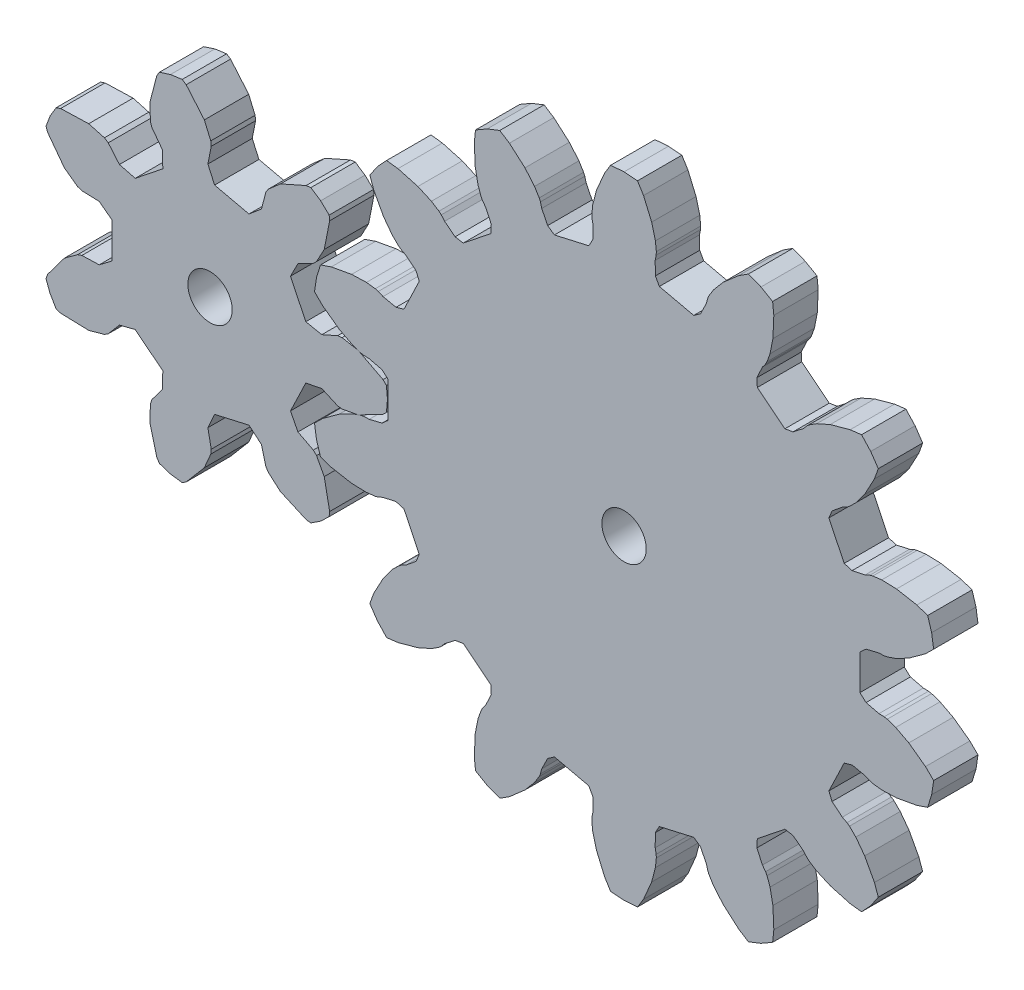
SolidWorks part; units mm, degrees
material "Corrugated Paper"
ref_plane "Front Plane" through (0, 0, 0) normal (0, 0, 1) x (1, 0, 0)
ref_plane "Top Plane" through (0, 0, 0) normal (0, 1, 0) x (1, 0, 0)
ref_plane "Right Plane" through (0, 0, 0) normal (1, 0, 0) x (0, 0, -1)
sketch "Model" plane through (0, 0, 0) normal (0, 0, 1) x (1, 0, 0)
  line L0 (10.824, -15.5893) -> (11.8775, -14.8939)
  line L1 (11.8775, -14.8939) -> (12.7899, -14.0216)
  line L2 (12.7899, -14.0216) -> (12.8434, -13.5144)
  line L3 (12.8434, -13.5144) -> (12.2623, -10.5576)
  line L4 (12.2623, -10.5576) -> (11.4342, -9.0171)
  line L5 (11.4342, -9.0171) -> (11.0892, -8.677)
  line L6 (11.0892, -8.677) -> (9.4401, -7.8202)
  line L7 (9.4401, -7.8202) -> (8.6391, -6.2612)
  line L8 (8.6391, -6.2612) -> (10.2816, -2.8505)
  line L9 (10.2816, -2.8505) -> (11.9999, -2.5047)
  line L10 (11.9999, -2.5047) -> (13.698, -3.2599)
  line L11 (13.698, -3.2599) -> (14.179, -3.3175)
  line L12 (14.179, -3.3175) -> (15.8632, -3.0111)
  line L13 (15.8632, -3.0111) -> (15.2951, -3.2054)
  line L14 (15.2951, -3.2054) -> (13.8858, -3.9376)
  line L15 (13.8858, -3.9376) -> (12.0928, -5.2415)
  line L16 (12.0928, -5.2415) -> (11.2168, -6.1052)
  line L17 (11.2168, -6.1052) -> (11.4324, -7.536)
  line L18 (11.4324, -7.536) -> (11.8589, -8.9187)
  line L19 (11.8589, -8.9187) -> (13.023, -9.3169)
  line L20 (13.023, -9.3169) -> (15.2041, -9.7136)
  line L21 (15.2041, -9.7136) -> (16.7916, -9.7618)
  line L22 (16.7916, -9.7618) -> (17.7443, -9.6477)
  line L23 (17.7443, -9.6477) -> (18.0633, -9.5598)
  line L24 (18.0633, -9.5598) -> (18.5734, -9.3329)
  line L25 (18.5734, -9.3329) -> (19.9687, -9.0348)
  line L26 (19.9687, -9.0348) -> (20.819, -9.2793)
  line L27 (20.819, -9.2793) -> (22.4615, -12.6899)
  line L28 (22.4615, -12.6899) -> (22.1225, -13.5071)
  line L29 (22.1225, -13.5071) -> (21.0194, -14.4122)
  line L30 (21.0194, -14.4122) -> (20.524, -14.6696)
  line L31 (20.524, -14.6696) -> (20.2564, -14.8641)
  line L32 (20.2564, -14.8641) -> (19.5731, -15.5378)
  line L33 (19.5731, -15.5378) -> (18.621, -16.809)
  line L34 (18.621, -16.809) -> (17.5714, -18.7617)
  line L35 (17.5714, -18.7617) -> (17.1569, -19.92)
  line L36 (17.1569, -19.92) -> (17.972, -21.1155)
  line L37 (17.972, -21.1155) -> (18.9562, -22.1762)
  line L38 (18.9562, -22.1762) -> (20.1777, -22.0299)
  line L39 (20.1777, -22.0299) -> (22.3149, -21.441)
  line L40 (22.3149, -21.441) -> (23.7661, -20.7956)
  line L41 (23.7661, -20.7956) -> (24.575, -20.2794)
  line L42 (24.575, -20.2794) -> (24.8242, -20.0619)
  line L43 (24.8242, -20.0619) -> (25.1854, -19.6361)
  line L44 (25.1854, -19.6361) -> (26.3132, -18.7621)
  line L45 (26.3132, -18.7621) -> (27.1854, -18.6134)
  line L46 (27.1854, -18.6134) -> (30.145, -20.9737)
  line L47 (30.145, -20.9737) -> (30.1941, -21.8571)
  line L48 (30.1941, -21.8571) -> (29.593, -23.151)
  line L49 (29.593, -23.151) -> (29.2583, -23.5979)
  line L50 (29.2583, -23.5979) -> (29.1016, -23.8893)
  line L51 (29.1016, -23.8893) -> (28.7783, -24.7928)
  line L52 (28.7783, -24.7928) -> (28.4721, -26.3512)
  line L53 (28.4721, -26.3512) -> (28.3736, -28.5659)
  line L54 (28.3736, -28.5659) -> (28.5027, -29.7893)
  line L55 (28.5027, -29.7893) -> (29.7558, -30.5128)
  line L56 (29.7558, -30.5128) -> (31.1028, -31.0414)
  line L57 (31.1028, -31.0414) -> (32.1398, -30.3796)
  line L58 (32.1398, -30.3796) -> (33.8099, -28.9217)
  line L59 (33.8099, -28.9217) -> (34.8374, -27.7106)
  line L60 (34.8374, -27.7106) -> (35.3421, -26.8946)
  line L61 (35.3421, -26.8946) -> (35.4723, -26.5904)
  line L62 (35.4723, -26.5904) -> (35.613, -26.0501)
  line L63 (35.613, -26.0501) -> (36.2499, -24.7734)
  line L64 (36.2499, -24.7734) -> (36.9712, -24.261)
  line L65 (36.9712, -24.261) -> (40.6618, -25.1033)
  line L66 (40.6618, -25.1033) -> (41.0893, -25.8779)
  line L67 (41.0893, -25.8779) -> (41.1092, -27.3046)
  line L68 (41.1092, -27.3046) -> (41.0015, -27.8524)
  line L69 (41.0015, -27.8524) -> (40.9868, -28.183)
  line L70 (40.9868, -28.183) -> (41.0875, -29.1372)
  line L71 (41.0875, -29.1372) -> (41.4877, -30.6741)
  line L72 (41.4877, -30.6741) -> (42.3599, -32.7123)
  line L73 (42.3599, -32.7123) -> (43.0071, -33.7585)
  line L74 (43.0071, -33.7585) -> (44.45, -33.8667)
  line L75 (44.45, -33.8667) -> (45.8929, -33.7585)
  line L76 (45.8929, -33.7585) -> (46.5401, -32.7123)
  line L77 (46.5401, -32.7123) -> (47.4123, -30.6741)
  line L78 (47.4123, -30.6741) -> (47.8125, -29.1372)
  line L79 (47.8125, -29.1372) -> (47.9132, -28.183)
  line L80 (47.9132, -28.183) -> (47.8985, -27.8524)
  line L81 (47.8985, -27.8524) -> (47.7908, -27.3046)
  line L82 (47.7908, -27.3046) -> (47.8107, -25.8779)
  line L83 (47.8107, -25.8779) -> (48.2382, -25.1033)
  line L84 (48.2382, -25.1033) -> (51.9288, -24.261)
  line L85 (51.9288, -24.261) -> (52.6501, -24.7734)
  line L86 (52.6501, -24.7734) -> (53.287, -26.0501)
  line L87 (53.287, -26.0501) -> (53.4277, -26.5904)
  line L88 (53.4277, -26.5904) -> (53.5579, -26.8946)
  line L89 (53.5579, -26.8946) -> (54.0626, -27.7106)
  line L90 (54.0626, -27.7106) -> (55.0901, -28.9217)
  line L91 (55.0901, -28.9217) -> (56.7602, -30.3796)
  line L92 (56.7602, -30.3796) -> (57.7972, -31.0414)
  line L93 (57.7972, -31.0414) -> (59.1442, -30.5128)
  line L94 (59.1442, -30.5128) -> (60.3973, -29.7893)
  line L95 (60.3973, -29.7893) -> (60.5264, -28.5659)
  line L96 (60.5264, -28.5659) -> (60.4279, -26.3512)
  line L97 (60.4279, -26.3512) -> (60.1217, -24.7928)
  line L98 (60.1217, -24.7928) -> (59.7984, -23.8893)
  line L99 (59.7984, -23.8893) -> (59.6417, -23.5979)
  line L100 (59.6417, -23.5979) -> (59.307, -23.151)
  line L101 (59.307, -23.151) -> (58.7059, -21.8571)
  line L102 (58.7059, -21.8571) -> (58.755, -20.9737)
  line L103 (58.755, -20.9737) -> (61.7146, -18.6134)
  line L104 (61.7146, -18.6134) -> (62.5868, -18.7621)
  line L105 (62.5868, -18.7621) -> (63.7146, -19.6361)
  line L106 (63.7146, -19.6361) -> (64.0758, -20.0619)
  line L107 (64.0758, -20.0619) -> (64.325, -20.2794)
  line L108 (64.325, -20.2794) -> (65.1339, -20.7956)
  line L109 (65.1339, -20.7956) -> (66.5851, -21.441)
  line L110 (66.5851, -21.441) -> (68.7223, -22.0299)
  line L111 (68.7223, -22.0299) -> (69.9438, -22.1762)
  line L112 (69.9438, -22.1762) -> (70.928, -21.1155)
  line L113 (70.928, -21.1155) -> (71.7431, -19.92)
  line L114 (71.7431, -19.92) -> (71.3286, -18.7617)
  line L115 (71.3286, -18.7617) -> (70.279, -16.809)
  line L116 (70.279, -16.809) -> (69.3269, -15.5378)
  line L117 (69.3269, -15.5378) -> (68.6436, -14.8641)
  line L118 (68.6436, -14.8641) -> (68.376, -14.6696)
  line L119 (68.376, -14.6696) -> (67.8806, -14.4122)
  line L120 (67.8806, -14.4122) -> (66.7775, -13.5071)
  line L121 (66.7775, -13.5071) -> (66.4385, -12.6899)
  line L122 (66.4385, -12.6899) -> (68.081, -9.2793)
  line L123 (68.081, -9.2793) -> (68.9313, -9.0348)
  line L124 (68.9313, -9.0348) -> (70.3266, -9.3329)
  line L125 (70.3266, -9.3329) -> (70.8367, -9.5598)
  line L126 (70.8367, -9.5598) -> (71.1557, -9.6477)
  line L127 (71.1557, -9.6477) -> (72.1084, -9.7618)
  line L128 (72.1084, -9.7618) -> (73.6959, -9.7136)
  line L129 (73.6959, -9.7136) -> (75.877, -9.3169)
  line L130 (75.877, -9.3169) -> (77.0411, -8.9187)
  line L131 (77.0411, -8.9187) -> (77.4676, -7.536)
  line L132 (77.4676, -7.536) -> (77.6832, -6.1052)
  line L133 (77.6832, -6.1052) -> (76.8072, -5.2415)
  line L134 (76.8072, -5.2415) -> (75.0142, -3.9376)
  line L135 (75.0142, -3.9376) -> (73.6049, -3.2054)
  line L136 (73.6049, -3.2054) -> (72.697, -2.8949)
  line L137 (72.697, -2.8949) -> (72.3715, -2.8357)
  line L138 (72.3715, -2.8357) -> (71.8134, -2.8188)
  line L139 (71.8134, -2.8188) -> (70.4269, -2.482)
  line L140 (70.4269, -2.482) -> (69.7669, -1.8928)
  line L141 (69.7669, -1.8928) -> (69.7669, 1.8928)
  line L142 (69.7669, 1.8928) -> (70.4269, 2.482)
  line L143 (70.4269, 2.482) -> (71.8134, 2.8188)
  line L144 (71.8134, 2.8188) -> (72.3715, 2.8357)
  line L145 (72.3715, 2.8357) -> (72.697, 2.8949)
  line L146 (72.697, 2.8949) -> (73.6049, 3.2054)
  line L147 (73.6049, 3.2054) -> (75.0142, 3.9376)
  line L148 (75.0142, 3.9376) -> (76.8072, 5.2415)
  line L149 (76.8072, 5.2415) -> (77.6832, 6.1052)
  line L150 (77.6832, 6.1052) -> (77.4676, 7.536)
  line L151 (77.4676, 7.536) -> (77.0411, 8.9187)
  line L152 (77.0411, 8.9187) -> (75.877, 9.3169)
  line L153 (75.877, 9.3169) -> (73.6959, 9.7136)
  line L154 (73.6959, 9.7136) -> (72.1084, 9.7618)
  line L155 (72.1084, 9.7618) -> (71.1557, 9.6477)
  line L156 (71.1557, 9.6477) -> (70.8367, 9.5598)
  line L157 (70.8367, 9.5598) -> (70.3266, 9.3329)
  line L158 (70.3266, 9.3329) -> (68.9313, 9.0348)
  line L159 (68.9313, 9.0348) -> (68.081, 9.2793)
  line L160 (68.081, 9.2793) -> (66.4385, 12.6899)
  line L161 (66.4385, 12.6899) -> (66.7775, 13.5071)
  line L162 (66.7775, 13.5071) -> (67.8806, 14.4122)
  line L163 (67.8806, 14.4122) -> (68.376, 14.6696)
  line L164 (68.376, 14.6696) -> (68.6436, 14.8641)
  line L165 (68.6436, 14.8641) -> (69.3269, 15.5378)
  line L166 (69.3269, 15.5378) -> (70.279, 16.809)
  line L167 (70.279, 16.809) -> (71.3286, 18.7617)
  line L168 (71.3286, 18.7617) -> (71.7431, 19.92)
  line L169 (71.7431, 19.92) -> (70.928, 21.1155)
  line L170 (70.928, 21.1155) -> (69.9438, 22.1762)
  line L171 (69.9438, 22.1762) -> (68.7223, 22.0299)
  line L172 (68.7223, 22.0299) -> (66.5851, 21.441)
  line L173 (66.5851, 21.441) -> (65.1339, 20.7956)
  line L174 (65.1339, 20.7956) -> (64.325, 20.2794)
  line L175 (64.325, 20.2794) -> (64.0758, 20.0619)
  line L176 (64.0758, 20.0619) -> (63.7146, 19.6361)
  line L177 (63.7146, 19.6361) -> (62.5868, 18.7621)
  line L178 (62.5868, 18.7621) -> (61.7146, 18.6134)
  line L179 (61.7146, 18.6134) -> (58.755, 20.9737)
  line L180 (58.755, 20.9737) -> (58.7059, 21.8571)
  line L181 (58.7059, 21.8571) -> (59.307, 23.151)
  line L182 (59.307, 23.151) -> (59.6417, 23.5979)
  line L183 (59.6417, 23.5979) -> (59.7984, 23.8893)
  line L184 (59.7984, 23.8893) -> (60.1217, 24.7928)
  line L185 (60.1217, 24.7928) -> (60.4279, 26.3512)
  line L186 (60.4279, 26.3512) -> (60.5264, 28.5659)
  line L187 (60.5264, 28.5659) -> (60.3973, 29.7893)
  line L188 (60.3973, 29.7893) -> (59.1442, 30.5128)
  line L189 (59.1442, 30.5128) -> (57.7972, 31.0414)
  line L190 (57.7972, 31.0414) -> (56.7602, 30.3796)
  line L191 (56.7602, 30.3796) -> (55.0901, 28.9217)
  line L192 (55.0901, 28.9217) -> (54.0626, 27.7106)
  line L193 (54.0626, 27.7106) -> (53.5579, 26.8946)
  line L194 (53.5579, 26.8946) -> (53.4277, 26.5904)
  line L195 (53.4277, 26.5904) -> (53.287, 26.0501)
  line L196 (53.287, 26.0501) -> (52.6501, 24.7734)
  line L197 (52.6501, 24.7734) -> (51.9288, 24.261)
  line L198 (51.9288, 24.261) -> (48.2382, 25.1033)
  line L199 (48.2382, 25.1033) -> (47.8107, 25.8779)
  line L200 (47.8107, 25.8779) -> (47.7908, 27.3046)
  line L201 (47.7908, 27.3046) -> (47.8985, 27.8524)
  line L202 (47.8985, 27.8524) -> (47.9132, 28.183)
  line L203 (47.9132, 28.183) -> (47.8125, 29.1372)
  line L204 (47.8125, 29.1372) -> (47.4123, 30.6741)
  line L205 (47.4123, 30.6741) -> (46.5401, 32.7123)
  line L206 (46.5401, 32.7123) -> (45.8929, 33.7585)
  line L207 (45.8929, 33.7585) -> (44.45, 33.8667)
  line L208 (44.45, 33.8667) -> (43.0071, 33.7585)
  line L209 (43.0071, 33.7585) -> (42.3599, 32.7123)
  line L210 (42.3599, 32.7123) -> (41.4877, 30.6741)
  line L211 (41.4877, 30.6741) -> (41.0875, 29.1372)
  line L212 (41.0875, 29.1372) -> (40.9868, 28.183)
  line L213 (40.9868, 28.183) -> (41.0015, 27.8524)
  line L214 (41.0015, 27.8524) -> (41.1092, 27.3046)
  line L215 (41.1092, 27.3046) -> (41.0893, 25.8779)
  line L216 (41.0893, 25.8779) -> (40.6618, 25.1033)
  line L217 (40.6618, 25.1033) -> (36.9712, 24.261)
  line L218 (36.9712, 24.261) -> (36.2499, 24.7734)
  line L219 (36.2499, 24.7734) -> (35.613, 26.0501)
  line L220 (35.613, 26.0501) -> (35.4723, 26.5904)
  line L221 (35.4723, 26.5904) -> (35.3421, 26.8946)
  line L222 (35.3421, 26.8946) -> (34.8374, 27.7106)
  line L223 (34.8374, 27.7106) -> (33.8099, 28.9217)
  line L224 (33.8099, 28.9217) -> (32.1398, 30.3796)
  line L225 (32.1398, 30.3796) -> (31.1028, 31.0414)
  line L226 (31.1028, 31.0414) -> (29.7558, 30.5128)
  line L227 (29.7558, 30.5128) -> (28.5027, 29.7893)
  line L228 (28.5027, 29.7893) -> (28.3736, 28.5659)
  line L229 (28.3736, 28.5659) -> (28.4721, 26.3512)
  line L230 (28.4721, 26.3512) -> (28.7783, 24.7928)
  line L231 (28.7783, 24.7928) -> (29.1016, 23.8893)
  line L232 (29.1016, 23.8893) -> (29.2583, 23.5979)
  line L233 (29.2583, 23.5979) -> (29.593, 23.151)
  line L234 (29.593, 23.151) -> (30.1941, 21.8571)
  line L235 (30.1941, 21.8571) -> (30.145, 20.9737)
  line L236 (30.145, 20.9737) -> (27.1854, 18.6134)
  line L237 (27.1854, 18.6134) -> (26.3132, 18.7621)
  line L238 (26.3132, 18.7621) -> (25.1854, 19.6361)
  line L239 (25.1854, 19.6361) -> (24.8242, 20.0619)
  line L240 (24.8242, 20.0619) -> (24.575, 20.2794)
  line L241 (24.575, 20.2794) -> (23.7661, 20.7956)
  line L242 (23.7661, 20.7956) -> (22.3149, 21.441)
  line L243 (22.3149, 21.441) -> (20.1777, 22.0299)
  line L244 (20.1777, 22.0299) -> (18.9562, 22.1762)
  line L245 (18.9562, 22.1762) -> (17.972, 21.1155)
  line L246 (17.972, 21.1155) -> (17.1569, 19.92)
  line L247 (17.1569, 19.92) -> (17.5714, 18.7617)
  line L248 (17.5714, 18.7617) -> (18.621, 16.809)
  line L249 (18.621, 16.809) -> (19.5731, 15.5378)
  line L250 (19.5731, 15.5378) -> (20.2564, 14.8641)
  line L251 (20.2564, 14.8641) -> (20.524, 14.6696)
  line L252 (20.524, 14.6696) -> (21.0194, 14.4122)
  line L253 (21.0194, 14.4122) -> (22.1225, 13.5071)
  line L254 (22.1225, 13.5071) -> (22.4615, 12.6899)
  line L255 (22.4615, 12.6899) -> (20.819, 9.2793)
  line L256 (20.819, 9.2793) -> (19.9687, 9.0348)
  line L257 (19.9687, 9.0348) -> (18.5734, 9.3329)
  line L258 (18.5734, 9.3329) -> (18.0633, 9.5598)
  line L259 (18.0633, 9.5598) -> (17.7443, 9.6477)
  line L260 (17.7443, 9.6477) -> (16.7916, 9.7618)
  line L261 (16.7916, 9.7618) -> (15.2041, 9.7136)
  line L262 (15.2041, 9.7136) -> (13.023, 9.3169)
  line L263 (13.023, 9.3169) -> (11.8589, 8.9187)
  line L264 (11.8589, 8.9187) -> (11.4324, 7.536)
  line L265 (11.4324, 7.536) -> (11.2168, 6.1052)
  line L266 (11.2168, 6.1052) -> (12.0928, 5.2415)
  line L267 (12.0928, 5.2415) -> (13.8858, 3.9376)
  line L268 (13.8858, 3.9376) -> (15.2951, 3.2054)
  line L269 (15.2951, 3.2054) -> (15.8632, 3.0111)
  line L270 (15.8632, 3.0111) -> (14.179, 3.3175)
  line L271 (14.179, 3.3175) -> (13.698, 3.2599)
  line L272 (13.698, 3.2599) -> (11.9999, 2.5047)
  line L273 (11.9999, 2.5047) -> (10.2816, 2.8505)
  line L274 (10.2816, 2.8505) -> (8.6391, 6.2612)
  line L275 (8.6391, 6.2612) -> (9.4401, 7.8202)
  line L276 (9.4401, 7.8202) -> (11.0892, 8.677)
  line L277 (11.0892, 8.677) -> (11.4342, 9.0171)
  line L278 (11.4342, 9.0171) -> (12.2623, 10.5576)
  line L279 (12.2623, 10.5576) -> (12.8434, 13.5144)
  line L280 (12.8434, 13.5144) -> (12.7899, 14.0216)
  line L281 (12.7899, 14.0216) -> (11.8775, 14.8939)
  line L282 (11.8775, 14.8939) -> (10.824, 15.5893)
  line L283 (10.824, 15.5893) -> (10.3177, 15.5286)
  line L284 (10.3177, 15.5286) -> (7.5643, 14.3042)
  line L285 (7.5643, 14.3042) -> (6.2467, 13.154)
  line L286 (6.2467, 13.154) -> (5.9919, 12.742)
  line L287 (5.9919, 12.742) -> (5.5235, 10.9436)
  line L288 (5.5235, 10.9436) -> (4.1818, 9.8158)
  line L289 (4.1818, 9.8158) -> (0.4912, 10.6581)
  line L290 (0.4912, 10.6581) -> (-0.2283, 12.2564)
  line L291 (-0.2283, 12.2564) -> (0.1301, 14.0799)
  line L292 (0.1301, 14.0799) -> (0.0792, 14.5617)
  line L293 (0.0792, 14.5617) -> (-0.6088, 16.1696)
  line L294 (-0.6088, 16.1696) -> (-2.5583, 18.4675)
  line L295 (-2.5583, 18.4675) -> (-2.9881, 18.7418)
  line L296 (-2.9881, 18.7418) -> (-4.239, 18.5724)
  line L297 (-4.239, 18.5724) -> (-5.4396, 18.1823)
  line L298 (-5.4396, 18.1823) -> (-5.7078, 17.7486)
  line L299 (-5.7078, 17.7486) -> (-6.4672, 14.8325)
  line L300 (-6.4672, 14.8325) -> (-6.3895, 13.0853)
  line L301 (-6.3895, 13.0853) -> (-6.2262, 12.6291)
  line L302 (-6.2262, 12.6291) -> (-5.1122, 11.1417)
  line L303 (-5.1122, 11.1417) -> (-5.067, 9.3895)
  line L304 (-5.067, 9.3895) -> (-8.0266, 7.0293)
  line L305 (-8.0266, 7.0293) -> (-9.7248, 7.4633)
  line L306 (-9.7248, 7.4633) -> (-10.927, 8.8804)
  line L307 (-10.927, 8.8804) -> (-11.3354, 9.141)
  line L308 (-11.3354, 9.141) -> (-13.0215, 9.6056)
  line L309 (-13.0215, 9.6056) -> (-16.0335, 9.5141)
  line L310 (-16.0335, 9.5141) -> (-16.516, 9.3491)
  line L311 (-16.516, 9.3491) -> (-17.1635, 8.2655)
  line L312 (-17.1635, 8.2655) -> (-17.607, 7.0837)
  line L313 (-17.607, 7.0837) -> (-17.4352, 6.6035)
  line L314 (-17.4352, 6.6035) -> (-15.6287, 4.1916)
  line L315 (-15.6287, 4.1916) -> (-14.2142, 3.163)
  line L316 (-14.2142, 3.163) -> (-13.7559, 3.0063)
  line L317 (-13.7559, 3.0063) -> (-11.8983, 2.9499)
  line L318 (-11.8983, 2.9499) -> (-10.5002, 1.8928)
  line L319 (-10.5002, 1.8928) -> (-10.5002, -1.8928)
  line L320 (-10.5002, -1.8928) -> (-11.8983, -2.9499)
  line L321 (-11.8983, -2.9499) -> (-13.7559, -3.0063)
  line L322 (-13.7559, -3.0063) -> (-14.2142, -3.163)
  line L323 (-14.2142, -3.163) -> (-15.6287, -4.1916)
  line L324 (-15.6287, -4.1916) -> (-17.4352, -6.6035)
  line L325 (-17.4352, -6.6035) -> (-17.607, -7.0837)
  line L326 (-17.607, -7.0837) -> (-17.1635, -8.2655)
  line L327 (-17.1635, -8.2655) -> (-16.516, -9.3491)
  line L328 (-16.516, -9.3491) -> (-16.0335, -9.5141)
  line L329 (-16.0335, -9.5141) -> (-13.0215, -9.6056)
  line L330 (-13.0215, -9.6056) -> (-11.3354, -9.141)
  line L331 (-11.3354, -9.141) -> (-10.927, -8.8804)
  line L332 (-10.927, -8.8804) -> (-9.7248, -7.4633)
  line L333 (-9.7248, -7.4633) -> (-8.0266, -7.0293)
  line L334 (-8.0266, -7.0293) -> (-5.067, -9.3895)
  line L335 (-5.067, -9.3895) -> (-5.1122, -11.1417)
  line L336 (-5.1122, -11.1417) -> (-6.2262, -12.6291)
  line L337 (-6.2262, -12.6291) -> (-6.3895, -13.0853)
  line L338 (-6.3895, -13.0853) -> (-6.4672, -14.8325)
  line L339 (-6.4672, -14.8325) -> (-5.7078, -17.7486)
  line L340 (-5.7078, -17.7486) -> (-5.4396, -18.1823)
  line L341 (-5.4396, -18.1823) -> (-4.239, -18.5724)
  line L342 (-4.239, -18.5724) -> (-2.9881, -18.7418)
  line L343 (-2.9881, -18.7418) -> (-2.5583, -18.4675)
  line L344 (-2.5583, -18.4675) -> (-0.6088, -16.1696)
  line L345 (-0.6088, -16.1696) -> (0.0792, -14.5617)
  line L346 (0.0792, -14.5617) -> (0.1301, -14.0799)
  line L347 (0.1301, -14.0799) -> (-0.2283, -12.2564)
  line L348 (-0.2283, -12.2564) -> (0.4912, -10.6581)
  line L349 (0.4912, -10.6581) -> (4.1818, -9.8158)
  line L350 (4.1818, -9.8158) -> (5.5235, -10.9436)
  line L351 (5.5235, -10.9436) -> (5.9919, -12.742)
  line L352 (5.9919, -12.742) -> (6.2467, -13.154)
  line L353 (6.2467, -13.154) -> (7.5643, -14.3042)
  line L354 (7.5643, -14.3042) -> (10.3177, -15.5286)
  line L355 (10.3177, -15.5286) -> (10.824, -15.5893)
  line L356 (15.9326, -2.9874) -> (18.5737, -1.6153)
  line L357 (18.5737, -1.6153) -> (18.9368, -1.2572)
  line L358 (18.9368, -1.2572) -> (19.05, 0)
  line L359 (19.05, 0) -> (18.9368, 1.2572)
  line L360 (18.9368, 1.2572) -> (18.5737, 1.6153)
  line L361 (18.5737, 1.6153) -> (15.9326, 2.9874)
  line L362 (15.9326, 2.9874) -> (16.203, 2.8949)
  line L363 (16.203, 2.8949) -> (16.5285, 2.8357)
  line L364 (16.5285, 2.8357) -> (17.0866, 2.8188)
  line L365 (17.0866, 2.8188) -> (18.4731, 2.482)
  line L366 (18.4731, 2.482) -> (19.1331, 1.8928)
  line L367 (19.1331, 1.8928) -> (19.1331, -1.8928)
  line L368 (19.1331, -1.8928) -> (18.4731, -2.482)
  line L369 (18.4731, -2.482) -> (17.0866, -2.8188)
  line L370 (17.0866, -2.8188) -> (16.5285, -2.8357)
  line L371 (16.5285, -2.8357) -> (16.203, -2.8949)
  line L372 (16.203, -2.8949) -> (15.9326, -2.9874)
  line L435 (15.8632, 3.0111) -> (15.9326, 2.9874)
  line L436 (15.9326, -2.9874) -> (15.8632, -3.0111)
  circle A0 centre (0, 0) radius 2.3813
  circle A1 centre (44.45, 0) radius 2.3812
  point P433 (44.45, 0)
  dimension "D2" = 4.7625
  dimension "D3" = 4.7625
  dimension "D1" = 44.45
extrude "Boss-Extrude2" add sketch "Model" along normal blind 4.7625 contours L436 L356 L357 L358 L359 L360 L361 L435 L270 L271 L272 L273 L274 L275 L276 L277 L278 L279 L280 L281 L282 L283 L284 L285 L286 L287 L288 L289 L290 L291 L292 L293 L294 L295 L296 L297 L298 L299 L300 L301 L302 L303 L304 L305 L306 L307 L308 L309 L310 L311 L312 region at (10.6332, -15.0384, 0)
extrude "Boss-Extrude3" add sketch "Model<4>" along normal blind 4.7625 separate body contours L372 L436 L13 L14 L15 L16 L17 L18 L19 L20 L21 L22 L23 L24 L25 L26 L27 L28 L29 L30 L31 L32 L33 L34 L35 L36 L37 L38 L39 L40 L41 L42 L43 L44 L45 L46 L47 L48 L49 L50 L51 L52 L53 L54 L55 L56 L57 L58 L59 L60 L61 region at (16.205, -3.8972, 0)
sketch "Model<4>" plane through (0, 0, 0) normal (0, 0, 1) x (1, 0, 0) same geometry as "Model"
equation "\"rodThick\"= 3/16in"
equation "\"thick\"= 3/16in"
equation "\"D1@Boss-Extrude2\"=\"thick\""
equation "\"D1@Boss-Extrude3\"=\"thick\""
equation "\"D2@Model\"=\"rodThick\""
equation "\"D3@Model\"=\"rodThick\""
